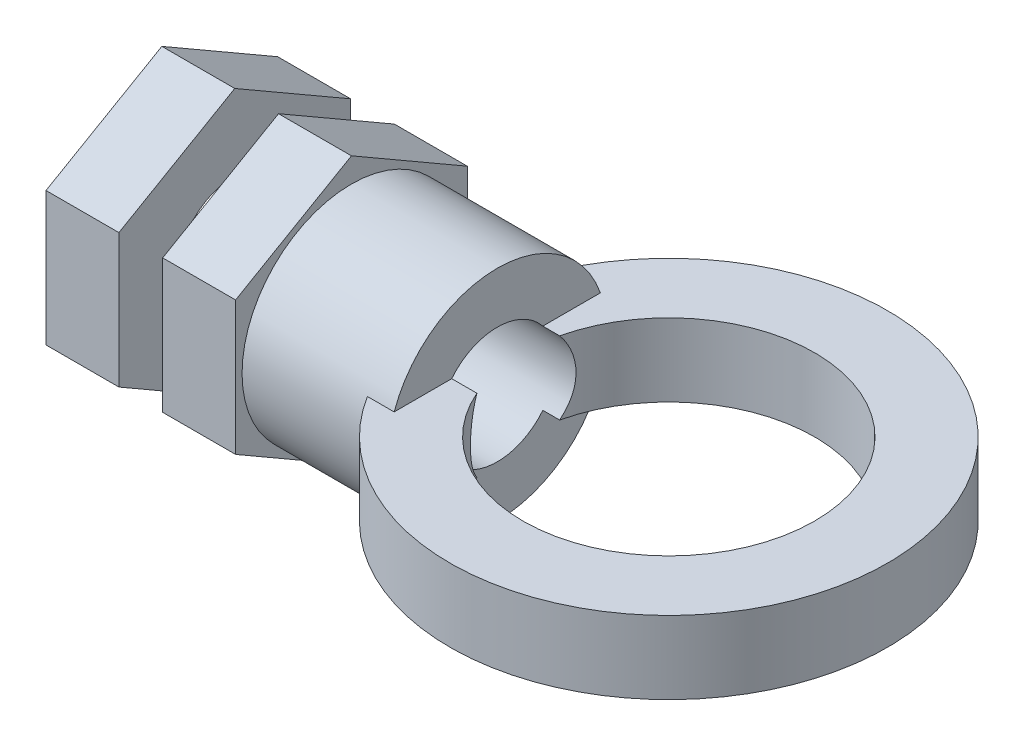
SolidWorks part; units mm, degrees
note: The reader was unsure of these and kept them because the rebuilt part matched: shared geometry of "Sketch3<2>", "Sketch1<3>".
ref_plane "Ebene vorne" through (0, 0, 0) normal (0, 0, 1) x (1, 0, 0)
ref_plane "Ebene oben" through (0, 0, 0) normal (0, 1, 0) x (1, 0, 0)
ref_plane "Ebene rechts" through (0, 0, 0) normal (1, 0, 0) x (0, 0, -1)
sketch "Sketch1" plane through (0, 0, 0) normal (1, 0, 0) x (0, 0, -1)
  circle A0 centre (0, 0) radius 7.5
  circle A1 centre (0, 0) radius 4
  dimension "D1" = 8
  dimension "D2" = 15
extrude "Boss-Extrude1" add sketch "Sketch1" along normal blind 10
sketch "Sketch2" plane through (0, 0, 0) normal (0, 1, 0) x (1, 0, 0)
  circle A0 centre (20.8967, 0.864) radius 15
  circle A1 centre (20.8967, 0.864) radius 10
  point P3 (20.8967, 0.864)
  dimension "D1" = 30
  dimension "D2" = 5
extrude "Boss-Extrude2" add sketch "Sketch2" along normal mid plane 5
sketch "Sketch3" plane through (0, 0, 0) normal (1, 0, 0) x (0, 0, -1)
  line L1 (0, -9.1734) -> (7.9444, -4.5867)
  line L2 (7.9444, -4.5867) -> (7.9444, 4.5867)
  line L3 (7.9444, 4.5867) -> (0, 9.1734)
  line L4 (0, 9.1734) -> (-7.9444, 4.5867)
  line L5 (-7.9444, 4.5867) -> (-7.9444, -4.5867)
  line L6 (-7.9444, -4.5867) -> (0, -9.1734)
  circle A0 centre (0, 0) radius 7.9444 construction
extrude "Boss-Extrude3" add sketch "Sketch3" against normal blind 5
extrude "Boss-Extrude4" add sketch "Sketch3<2>" against normal blind 5 from offset 8 separate body offset against normal yes
sketch "Sketch3<2>" plane through (0, 0, 0) normal (1, 0, 0) x (0, 0, -1) same geometry as "Sketch3"
extrude "Cut-Extrude1" cut sketch "Sketch1<3>" against normal through all and the other way up to next contours A1
sketch "Sketch1<3>" plane through (0, 0, 0) normal (1, 0, 0) x (0, 0, -1) same geometry as "Sketch1"
